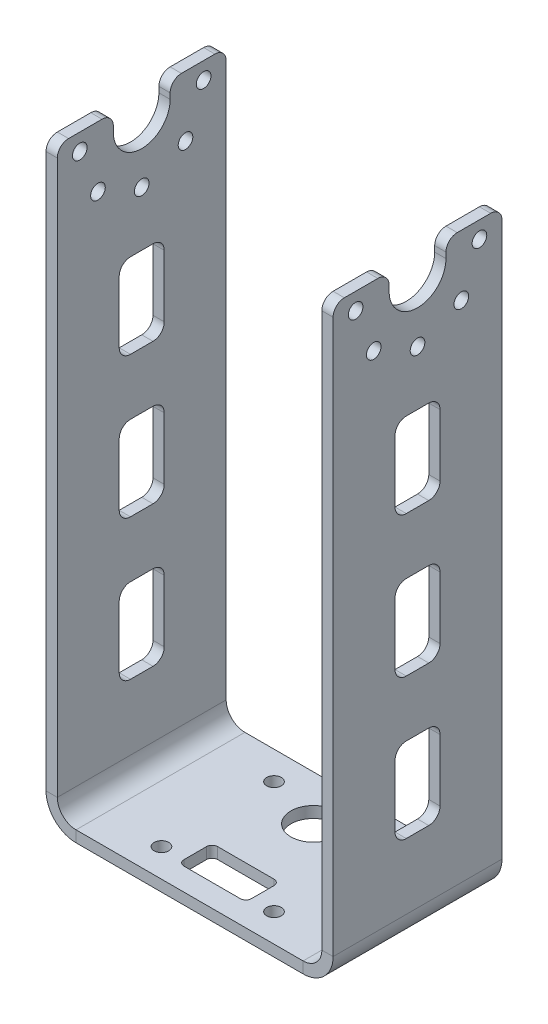
SolidWorks part; units mm, degrees
note: The reader was unsure of these and kept them because the rebuilt part matched: bend radius of "Base-Flange1", "BaseBend1", "BaseBend2".
material "2024 Alloy (SN)"
ref_plane "Front Plane" through (0, 0, 0) normal (0, 0, 1) x (1, 0, 0)
ref_plane "Top Plane" through (0, 0, 0) normal (0, 1, 0) x (1, 0, 0)
ref_plane "Right Plane" through (0, 0, 0) normal (1, 0, 0) x (0, 0, -1)
sketch "Sketch1" plane through (0, 0, 0) normal (0, 0, 1) x (1, 0, 0)
  line L0 (-23.5, 103.7) -> (-23.5, 0)
  line L1 (-23.5, 0) -> (23.5, 0)
  line L2 (23.5, 0) -> (23.5, 103.7)
  point P5 (0, 0)
  dimension "D1" = 103.7
  dimension "D2" = 47
sheet metal parameters "Sheet-Metal1" thickness 2 parameters "D1"=3.33
base flange "Base-Flange1" sketch "Sketch1" end condition mid plane depth 30 reverse direction no thickness 2 reverse thickness direction no bend radius 3.33
bend "BaseBend1" bend radius 3.33 bend angle 90 parameters "D5"=1
bend "BaseBend2" bend radius 3.33 bend angle 90 parameters "D5"=2
sketch "Sketch5" plane through (0, -2, 0) normal (0, -1, 0) x (1, 0, 0)
  line L2 (-10, 10) -> (10, 10)
  line L3 (-10, 10) -> (-10, -10)
  line L4 (-10, -10) -> (10, -10)
  line L5 (10, 10) -> (10, -10)
  line L6 (-10, 10) -> (10, -10) construction
  line L7 (-10, -10) -> (10, 10) construction
  circle A9 centre (-10, 10) radius 1.3
  circle A10 centre (10, 10) radius 1.3
  circle A11 centre (10, -10) radius 1.3
  circle A12 centre (-10, -10) radius 1.3
  point P0 (0, 0)
  dimension "D1" = 20
  dimension "D2" = 20
  dimension "D9" = 2.6
extrude "Cut-Extrude1" cut sketch "Sketch5" against normal blind 10 contours L2 A9 L3 | L3 A9 L2 | L5 A10 L2 | L2 A10 L5 | L4 A11 L5 | L5 A11 L4 | L3 A12 L4 | L4 A12 L3 normal cut yes
sketch "Sketch6" plane through (0, 0, 0) normal (1, 0, 0) x (0, 0, -1)
  line L0 (-15, 103.7) -> (15, 103.7) construction
  line L1 (-5.05, 100.7) -> (-5.05, 103.7)
  line L2 (-5.05, 103.7) -> (5.05, 103.7)
  line L3 (5.05, 103.7) -> (5.05, 100.7)
  circle A0 centre (0, 100.7) radius 5.05
  circle A1 centre (0, 89.7) radius 1.3
  circle A2 centre (-7.7782, 92.9218) radius 1.3
  circle A3 centre (-11, 100.7) radius 1.3
  circle A4 centre (-7.7782, 108.4782) radius 1.3
  circle A5 centre (0, 111.7) radius 1.3
  circle A6 centre (7.7782, 108.4782) radius 1.3
  circle A7 centre (11, 100.7) radius 1.3
  circle A8 centre (7.7782, 92.9218) radius 1.3
  point P6 (0, 103.7)
  point P28 (0, 100.7)
  dimension "D1" = 10.1
  dimension "D2" = 3
  dimension "D4" = 2.6
  dimension "D3" = 11
extrude "Cut-Extrude2" cut sketch "Sketch6" along normal through all and the other way through all contours A0 L2 | A0 L2 L1 | A0 L3 L2 | A7 | A1 | A2 | A8 | A3 normal cut yes
sketch "Sketch8" plane through (0, 0, 0) normal (0, 1, 0) x (1, 0, 0)
  line L2 (-6, -5) -> (6, -5)
  line L3 (-6, -5) -> (-6, -11)
  line L4 (-6, -11) -> (6, -11)
  line L5 (6, -5) -> (6, -11)
  line L7 (-20.17, -15) -> (20.17, -15) construction
  circle A0 centre (0, -1) radius 1 construction
  circle A1 centre (-5.6569, 1.3431) radius 1 construction
  circle A2 centre (-8, 7) radius 1 construction
  circle A3 centre (-5.6569, 12.6569) radius 1 construction
  circle A4 centre (0, 15) radius 1 construction
  circle A5 centre (5.6569, 12.6569) radius 1 construction
  circle A6 centre (8, 7) radius 1 construction
  circle A7 centre (5.6569, 1.3431) radius 1 construction
  circle A8 centre (0, 7) radius 4
  point P19 (0, 7)
  point P31 (0, -5)
  dimension "D6" = 22
  dimension "D7" = 8
  dimension "D1" = 8
  dimension "D3" = 2
  dimension "D2" = 8
  dimension "D8" = 6
  dimension "D9" = 12
  dimension "D12" = 5
extrude "Cut-Extrude4" cut sketch "Sketch8" against normal blind 10 normal cut yes
sketch "Sketch9" plane through (0, 0, 0) normal (1, 0, 0) x (0, 0, -1)
  line L0 (-2, 40) -> (2, 40)
  line L1 (-2, 15) -> (2, 15)
  line L2 (4, 17) -> (4, 28)
  line L3 (4, 42) -> (4, 53)
  line L4 (2, 55) -> (-2, 55)
  line L5 (2, 30) -> (-2, 30)
  line L6 (-4, 53) -> (-4, 42)
  line L7 (-2, 65) -> (2, 65)
  line L8 (-4, 28) -> (-4, 17)
  line L9 (4, 67) -> (4, 78)
  line L10 (2, 80) -> (-2, 80)
  line L11 (-15, 3.33) -> (-15, 103.7) construction
  line L12 (15, 3.33) -> (15, 103.7) construction
  line L13 (-4, 78) -> (-4, 67)
  arc A0 (-4, 42) -> (-2, 40) centre (-2, 42) ccw
  arc A1 (-4, 17) -> (-2, 15) centre (-2, 17) ccw
  arc A2 (2, 15) -> (4, 17) centre (2, 17) ccw
  arc A3 (2, 30) -> (4, 28) centre (2, 28) cw
  arc A4 (-2, 30) -> (-4, 28) centre (-2, 28) ccw
  arc A5 (2, 40) -> (4, 42) centre (2, 42) ccw
  arc A6 (2, 55) -> (4, 53) centre (2, 53) cw
  arc A7 (-2, 55) -> (-4, 53) centre (-2, 53) ccw
  arc A8 (-4, 67) -> (-2, 65) centre (-2, 67) ccw
  arc A9 (2, 65) -> (4, 67) centre (2, 67) ccw
  arc A10 (2, 80) -> (4, 78) centre (2, 78) cw
  arc A11 (-2, 80) -> (-4, 78) centre (-2, 78) ccw
  point P23 (-4, 30)
  dimension "D3" = 3
  dimension "D7" = 2
  dimension "D1" = 11
  dimension "D2" = 11
  dimension "D4" = 15
  dimension "D5" = 15
extrude "Cut-Extrude5" cut sketch "Sketch9" against normal through all and the other way through all normal cut yes
fillet "Fillet1" radius 2 8 edges at (24.5, 103.7, -5.05) (24.5, 103.7, 15) (-24.5, 103.7, 15) (-24.5, 103.7, -5.05) (-24.5, 103.7, -15) (24.5, 103.7, -15) (-24.5, 103.7, 5.05) (24.5, 103.7, 5.05)
fillet "Fillet2" radius 1 4 edges at (-6, -1, 11) (6, -1, 11) (6, -1, 5) (-6, -1, 5)
flat pattern "Flat-Pattern1" [suppressed]
sketch "Bend-Lines1" plane through (23.5, 0, 0) normal (-1, 0, 0) x (0, 0, 1)
  line L0 (15, -47.2123) -> (-15, -47.2123) construction
  line L1 (15, -0.0708) -> (-15, -0.0708) construction
  line L2 (15, -47.2123) -> (-15, -47.2123) construction
  line L3 (15, -0.0708) -> (-15, -0.0708) construction
sketch3d "Bounding-Box1" [suppressed]
  line L0 (0.0001, 103.7, 0) -> (0, -150.9831, 0) construction
  line L1 (-29.9999, 103.7, 0) -> (-30, -150.9831, 0) construction
  line L2 (0.0001, 103.7, 0) -> (-29.9999, 103.7, 0) construction
  line L3 (0, -150.9831, 0) -> (-30, -150.9831, 0) construction
bend of the flat pattern "Flatten-<BaseBend1>1"
bend of the flat pattern "Flatten-<BaseBend2>1"
